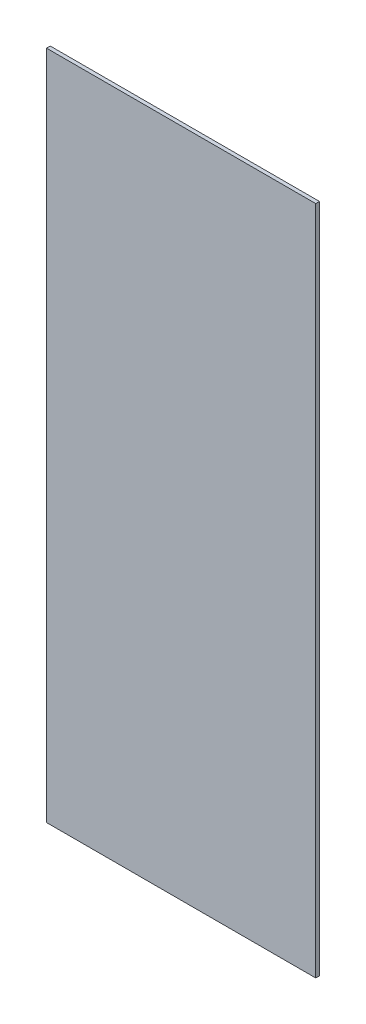
SolidWorks part; units mm, degrees
material "Acrylic (Medium-high impact)"
ref_plane "Front Plane" through (0, 0, 0) normal (0, 0, 1) x (1, 0, 0)
ref_plane "Top Plane" through (0, 0, 0) normal (0, 1, 0) x (1, 0, 0)
ref_plane "Right Plane" through (0, 0, 0) normal (1, 0, 0) x (0, 0, -1)
sketch "Sketch1" plane through (0, 0, 0) normal (0, 0, 1) x (1, 0, 0)
  line L1 (0, 0) -> (229.4196, 0)
  line L2 (0, 0) -> (0, 571.5)
  line L3 (0, 571.5) -> (229.4196, 571.5)
  line L4 (229.4196, 0) -> (229.4196, 571.5)
  point P7 (237.5767, -5.8958)
  dimension "D1" = 571.5
  dimension "D2" = 229.4196
extrude "Boss-Extrude1" add sketch "Sketch1" along normal blind 3.175
